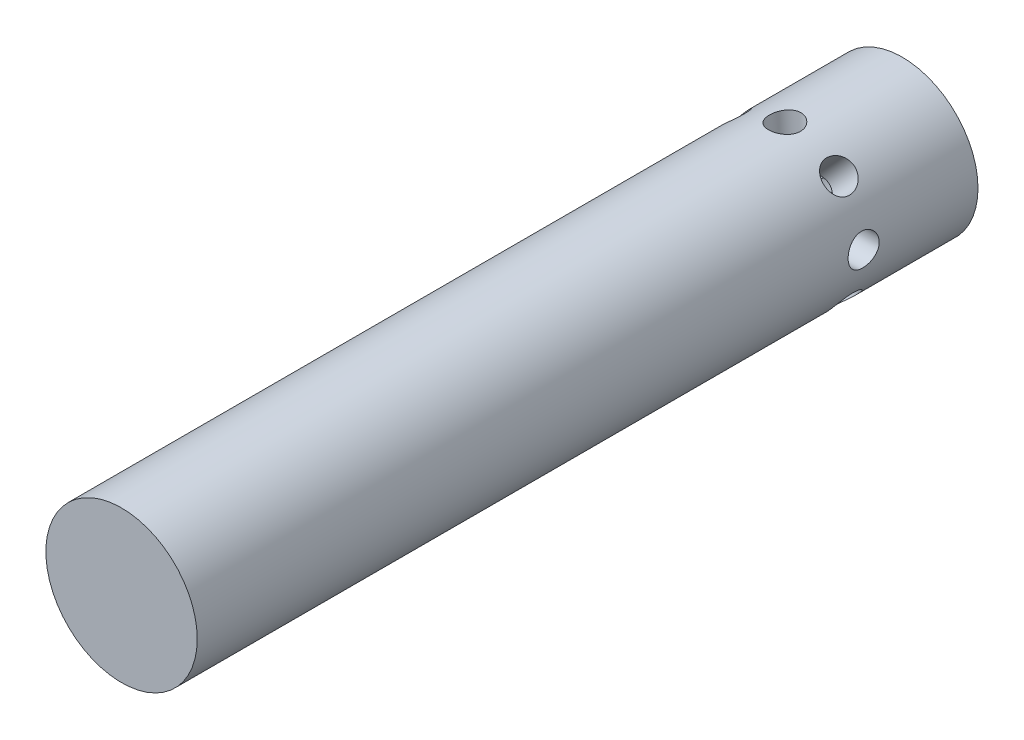
SolidWorks part; units mm, degrees
ref_plane "Front Plane" through (0, 0, 0) normal (0, 0, 1) x (1, 0, 0)
ref_plane "Top Plane" through (0, 0, 0) normal (0, 1, 0) x (1, 0, 0)
ref_plane "Right Plane" through (0, 0, 0) normal (1, 0, 0) x (0, 0, -1)
sketch "Sketch1" plane through (0, 0, 0) normal (0, 0, 1) x (1, 0, 0)
  circle A0 centre (0, 0) radius 19.875
  dimension "D1" = 39.75
extrude "Boss-Extrude1" add sketch "Sketch1" against normal blind 205
sketch "Sketch3" plane through (0, 0, -205) normal (0, 0, -1) x (-1, 0, 0)
  circle A0 centre (0, 0) radius 10
  dimension "D1" = 20
extrude "Cut-Extrude1" cut sketch "Sketch3" against normal blind 50
sketch "Sketch4" plane through (0, 0, -205) normal (0, 0, -1) x (-1, 0, 0)
  circle A0 centre (0, 0) radius 19.875 construction
  point P0 (-0.8422, -19.8571)
ref_plane "Plane1" through (0.8422, -19.8571, -205) normal (0.0424, -0.9991, 0) x (-0.9991, -0.0424, 0)
sketch "Sketch6" plane through (0.8422, -19.8571, -205) normal (0.0424, -0.9991, 0) x (-0.9991, -0.0424, 0)
  line L0 (0, -30) -> (0, 0) construction
  line L1 (19.875, 0) -> (-19.875, 0) construction
  circle A0 centre (0, -30) radius 4.0759
  dimension "D1" = 30
extrude "Cut-Extrude2" cut sketch "Sketch6" against normal blind 10
pattern_circular "CirPattern1" count 8 over 360 about axis through (0, 0, -205) along (0, 0, 1) of "Cut-Extrude2" reverse direction yes
